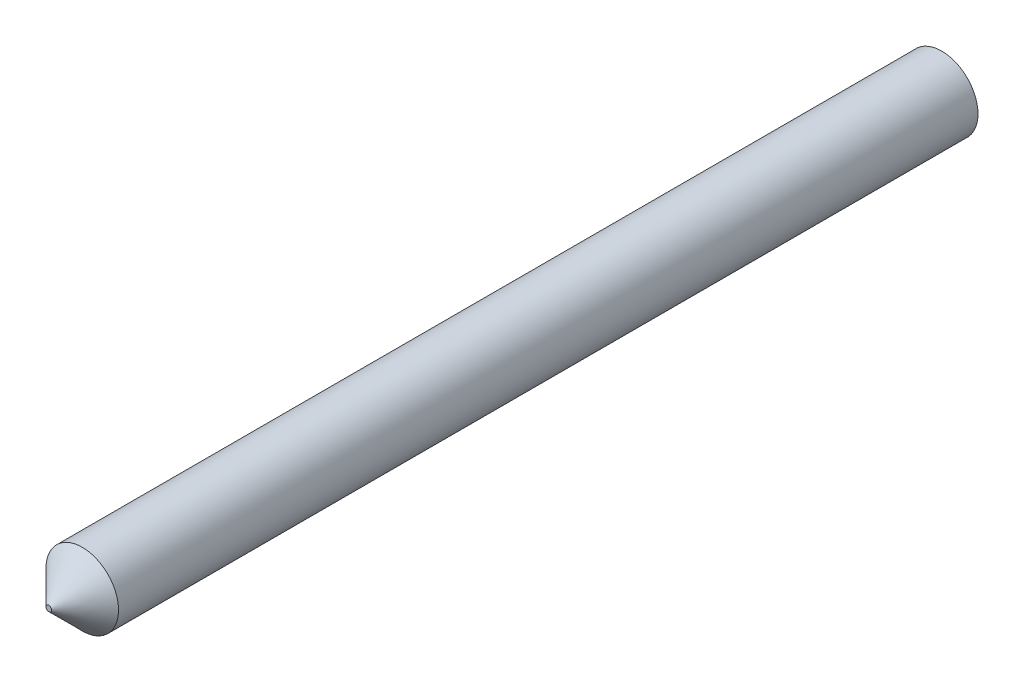
SolidWorks part; units mm, degrees
ref_plane "Alzado" through (0, 0, 0) normal (0, 0, 1) x (1, 0, 0)
ref_plane "Planta" through (0, 0, 0) normal (0, 1, 0) x (1, 0, 0)
ref_plane "Vista lateral" through (0, 0, 0) normal (1, 0, 0) x (0, 0, -1)
sketch "Croquis1" plane through (0, 0, 0) normal (0, 0, 1) x (1, 0, 0)
  circle A0 centre (0, 0) radius 1.625
  dimension "D1" = 3.25
extrude "Saliente-Extruir1" add sketch "Croquis1" along normal blind 40
chamfer "Chaflán1" distance 1.5 angle 45 1 edges at (1.625, 0, 40)
